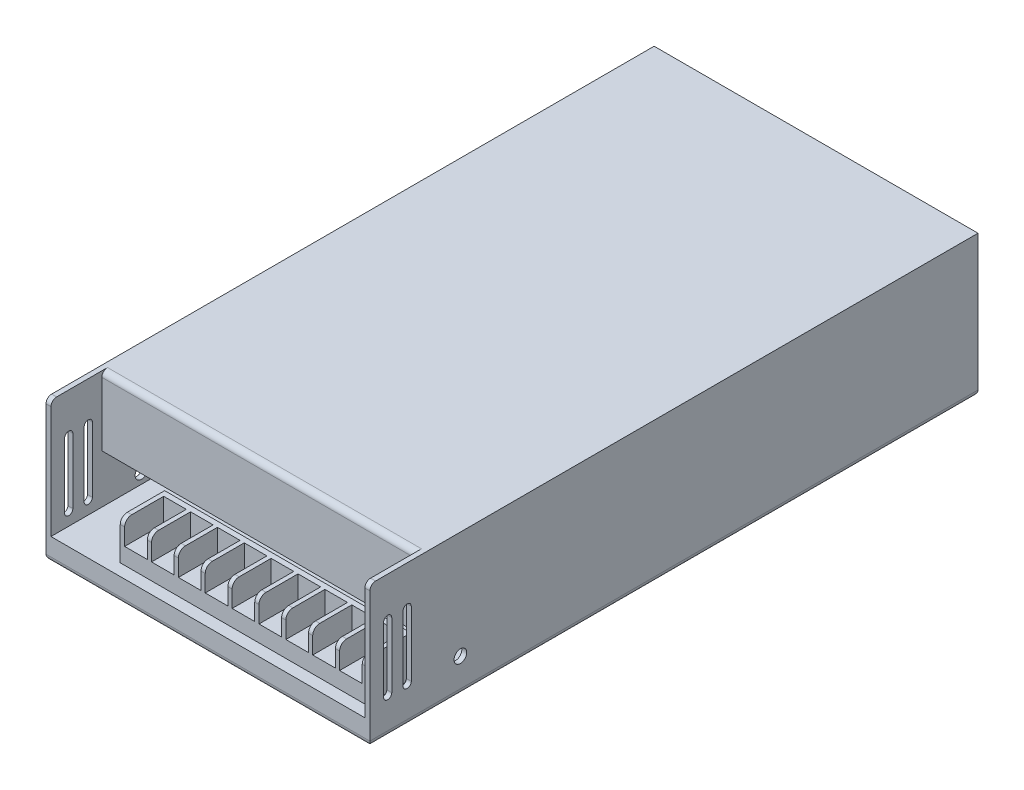
SolidWorks part; units mm, degrees
material "2024 Alloy"
ref_plane "Front Plane" through (0, 0, 0) normal (0, 0, 1) x (1, 0, 0)
ref_plane "Top Plane" through (0, 0, 0) normal (0, 1, 0) x (1, 0, 0)
ref_plane "Right Plane" through (0, 0, 0) normal (1, 0, 0) x (0, 0, -1)
sketch "Sketch1" plane through (0, 0, 0) normal (0, 1, 0) x (1, 0, 0)
  line L0 (0, 197) -> (0, -18) construction
  line L1 (-57.25, -18) -> (57.25, -18)
  line L2 (-57.25, -18) -> (-57.25, 197)
  line L3 (-57.25, 197) -> (57.25, 197)
  line L4 (57.25, -18) -> (57.25, 197)
  line L5 (-57.25, 0) -> (57.25, 0) construction
  dimension "D1" = 215
  dimension "D2" = 18
  dimension "D3" = 114.5
extrude "Boss-Extrude1" add sketch "Sketch1" along normal blind 41.75 and the other way blind 8.25
sketch "Sketch2" plane through (0, 0, 18) normal (0, 0, 1) x (1, 0, 0)
  line L0 (-57.25, 41.75) -> (57.25, 41.75) construction
  line L1 (-55.5, 0) -> (55.5, 0)
  line L2 (-55.5, 0) -> (-55.5, 41.75)
  line L3 (-55.5, 41.75) -> (55.5, 41.75)
  line L4 (55.5, 0) -> (55.5, 41.75)
  line L5 (0, 0) -> (0, 41.75) construction
  line L6 (57.25, -8.25) -> (57.25, 41.75) construction
  dimension "D1" = 1.75
extrude "Cut-Extrude1" cut sketch "Sketch2" against normal blind 18
sketch "Sketch3" plane through (57.25, 0, 0) normal (1, 0, 0) x (0, 0, -1)
  line L0 (-11.71, 27.7) -> (-11.71, 4.7) construction
  line L1 (-10.26, 27.7) -> (-10.26, 4.7)
  line L2 (-13.16, 27.7) -> (-13.16, 4.7)
  line L3 (-4.81, 27.7) -> (-4.81, 4.7) construction
  line L4 (-3.36, 27.7) -> (-3.36, 4.7)
  line L5 (-6.26, 27.7) -> (-6.26, 4.7)
  line L6 (-11.71, 16.2) -> (-4.81, 16.2) construction
  line L7 (-18, -8.25) -> (-18, 41.75) construction
  line L8 (-11.71, 29.15) -> (-11.71, 41.75) construction
  line L9 (-18, 41.75) -> (197, 41.75) construction
  line L10 (-11.71, 3.25) -> (-11.71, -8.25) construction
  line L11 (-18, -8.25) -> (197, -8.25) construction
  arc A0 (-10.26, 27.7) -> (-13.16, 27.7) centre (-11.71, 27.7) ccw
  arc A1 (-13.16, 4.7) -> (-10.26, 4.7) centre (-11.71, 4.7) ccw
  arc A2 (-3.36, 27.7) -> (-6.26, 27.7) centre (-4.81, 27.7) ccw
  arc A3 (-6.26, 4.7) -> (-3.36, 4.7) centre (-4.81, 4.7) ccw
  point P2 (-11.71, 16.2)
  point P7 (-4.81, 16.2)
  dimension "D1" = 4.84
  dimension "D2" = 2.9
  dimension "D3" = 4
  dimension "D4" = 12.6
  dimension "D5" = 11.5
extrude "Cut-Extrude2" cut sketch "Sketch3" against normal through all
fillet "Fillet1" radius 2 7 edges at (0, -8.25, -197) (-57.25, -8.25, -89.5) (0, -8.25, 18) (57.25, -8.25, -89.5) (0, 41.75, 0) (56.375, 41.75, 18) (-56.375, 41.75, 18)
sketch "Sketch4" plane through (0, 0, 0) normal (0, 1, 0) x (-1, 0, 0)
  line L0 (55.5, 0) -> (-55.5, 0) construction
  line L1 (35.2, 0) -> (-51.85, 0)
  line L2 (35.2, 0) -> (35.2, 13.8)
  line L3 (35.2, 13.8) -> (-51.85, 13.8)
  line L4 (-51.85, 0) -> (-51.85, 13.8)
  line L5 (55.5, 18) -> (-55.5, 18) construction
  line L6 (-55.5, 0) -> (-55.5, 18) construction
  line L7 (55.5, 0) -> (55.5, 18) construction
  dimension "D1" = 4.2
  dimension "D2" = 3.65
  dimension "D3" = 20.3
extrude "Boss-Extrude2" add sketch "Sketch4" along normal blind 14.25 separate body
sketch "Sketch7" plane through (0, 0, 0) normal (0, 0, 1) x (1, 0, 0)
  line L0 (-55.5, 39.75) -> (-55.5, 0) construction
  line L1 (-55.5, 17.25) -> (55.5, 17.25)
  line L2 (-55.5, 17.25) -> (-55.5, 0)
  line L3 (-55.5, 0) -> (55.5, 0)
  line L4 (55.5, 17.25) -> (55.5, 0)
  line L5 (-55.5, 0) -> (55.5, 0) construction
  line L6 (51.85, 14.25) -> (-35.2, 14.25) construction
  line L7 (55.5, 0) -> (55.5, 39.75) construction
  dimension "D1" = 3
extrude "Cut-Extrude4" cut sketch "Sketch7" against normal offset from surface (195.25 mm away) 1.75 up to face at (0, 17.75, -197)
fillet "Fillet2" radius 2.5 1 edges at (8.325, 14.25, 13.8)
sketch "Sketch6" plane through (0, 0, 13.8) normal (0, 0, 1) x (1, 0, 0)
  line L0 (-35.2, 14.25) -> (51.85, 14.25) construction
  line L1 (42.35, 14.25) -> (50.35, 14.25)
  line L2 (42.35, 14.25) -> (42.35, 5.8)
  line L3 (42.35, 5.8) -> (50.35, 5.8)
  line L4 (50.35, 14.25) -> (50.35, 5.8)
  line L6 (51.85, 11.75) -> (51.85, 0) construction
  line L7 (-35.2, 0) -> (51.85, 0) construction
  dimension "D1" = 5.8
  dimension "D2" = 1.5
  dimension "D3" = 8
extrude "Cut-Extrude3" cut sketch "Sketch6" against normal up to surface (13.8 mm away) up to face at (0, 28.5, 0)
sketch "Sketch9" plane through (0, 0, 0) normal (0, 0, -1) x (-1, 0, 0)
  line L0 (35.2, 14.25) -> (35.2, 0) construction
  line L1 (-51.85, 14.25) -> (35.2, 14.25)
  line L2 (-51.85, 14.25) -> (-51.85, 0.5)
  line L3 (-51.85, 0.5) -> (35.2, 0.5)
  line L4 (35.2, 14.25) -> (35.2, 0.5)
  line L5 (-51.85, 0) -> (35.2, 0) construction
  dimension "D1" = 0.5
extrude "Boss-Extrude6" add sketch "Sketch9" along normal blind 1.9
pattern_linear "LPattern1" count 9 spacing 9.5 along (1, 0, 0) of "Cut-Extrude3"
hole_wizard "M3 Clearance Hole2" positions "Sketch14" profile "Sketch13" hole size "M3" standard "Ansi Metric"
sketch "Sketch14" plane through (0, -8.25, 0) normal (0, -1, 0) x (1, 0, 0)
  line L0 (-57.25, 18) -> (57.25, 18) construction
  line L2 (-57.25, -197) -> (-57.25, 18) construction
  line L3 (57.25, -197) -> (-57.25, -197) construction
  line L4 (57.25, 18) -> (57.25, -197) construction
  point P0 (-47.5, -8.75)
  point P1 (47.5, -8.75)
  point P3 (47.5, -187.25)
  point P5 (-47.5, -187.25)
  dimension "D1" = 26.75
  dimension "D2" = 9.75
  dimension "D3" = 9.75
  dimension "D4" = 9.75
sketch "Sketch13" plane through (-47.5, -8.25, -8.75) normal (1, 0, 0) x (0, 0, -1)
  line L0 (0, 0) -> (0, 3.0215)
  line L1 (0, 3.0215) -> (1.7, 2)
  line L2 (1.7, 2) -> (1.7, 0)
  line L5 (1.7, 0) -> (0, 0)
  line L10 (0, 3.0215) -> (-1.7, 2) construction
  line L11 (0, -6.35) -> (0, 107.95) construction
  dimension "Hole Dia." = 3.4
  dimension "Hole Depth" = 2
  dimension "Drill Angle" = 118
hole_wizard "M4 Clearance Hole1" positions "Sketch16" profile "Sketch15" hole size "M4" standard "Ansi Metric"
sketch "Sketch16" plane through (57.25, 0, 0) normal (1, 0, 0) x (0, 0, -1)
  line L0 (-18, -6.25) -> (-18, 39.75) construction
  line L1 (195, -8.25) -> (-16, -8.25) construction
  point P0 (14, 3.75)
  dimension "D1" = 32
  dimension "D2" = 12
sketch "Sketch15" plane through (57.25, 3.75, -14) normal (0, 1, 0) x (0, 0, -1)
  line L0 (0, 0) -> (0, 3.3519)
  line L1 (0, 3.3519) -> (2.25, 2)
  line L2 (2.25, 2) -> (2.25, 0)
  line L5 (2.25, 0) -> (0, 0)
  line L10 (0, 3.3519) -> (-2.25, 2) construction
  line L11 (0, -6.35) -> (0, 107.95) construction
  dimension "Hole Dia." = 4.5
  dimension "Hole Depth" = 2
  dimension "Drill Angle" = 118
mirror "M4 Hole Other Side" about plane through (0, 0, 0) normal (1, 0, 0) of "M4 Clearance Hole1"
